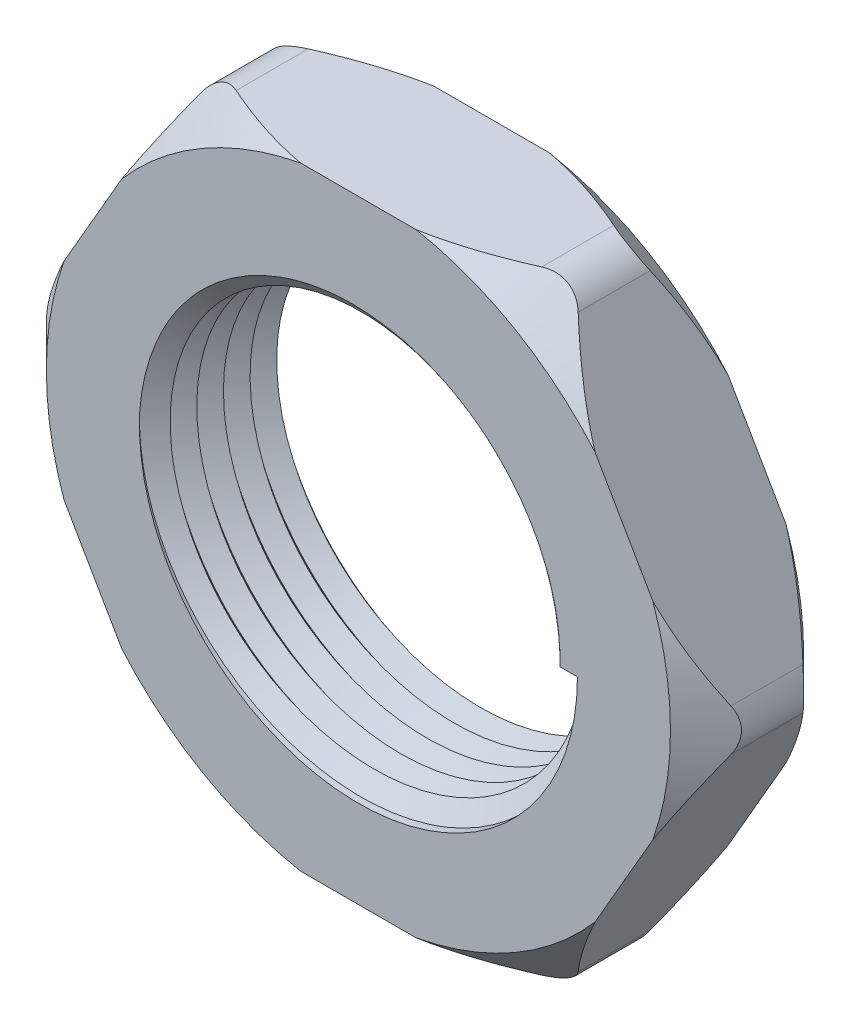
SolidWorks part; units mm, degrees
material "AISI 321 Annealed Stainless Steel (SS)"
ref_plane "Front Plane" through (0, 0, 0) normal (0, 0, 1) x (1, 0, 0)
ref_plane "Top Plane" through (0, 0, 0) normal (0, 1, 0) x (1, 0, 0)
ref_plane "Right Plane" through (0, 0, 0) normal (1, 0, 0) x (0, 0, -1)
sketch "Sketch1" plane through (0, 0, 0) normal (0, 0, 1) x (1, 0, 0)
  line L1 (12.8316, 0) -> (6.4158, 11.1125)
  line L2 (6.4158, 11.1125) -> (-6.4158, 11.1125)
  line L3 (-6.4158, 11.1125) -> (-12.8316, 0)
  line L4 (-12.8316, 0) -> (-6.4158, -11.1125)
  line L5 (-6.4158, -11.1125) -> (6.4158, -11.1125)
  line L6 (6.4158, -11.1125) -> (12.8316, 0)
  circle A0 centre (0, 0) radius 11.1125 construction
  circle A1 centre (0, 0) radius 7.9375
  dimension "D2" = 15.875
  dimension "D1" = 22.225
extrude "Boss-Extrude1" add sketch "Sketch1" along normal blind 4.826
sketch "Sketch2" plane through (0, 0, 0) normal (0, 1, 0) x (1, 0, 0)
  line L0 (11.3076, 0) -> (12.8316, -1.524)
  line L1 (12.8316, 0) -> (6.4158, 0) construction
  line L2 (12.8316, -4.826) -> (12.8316, 0) construction
  line L3 (12.8316, -1.524) -> (13.3729, -1.524)
  line L4 (13.3729, -1.524) -> (13.3729, 0.9545)
  line L5 (13.3729, 0.9545) -> (11.3076, 0.9545)
  line L6 (11.3076, 0.9545) -> (11.3076, 0)
  line L7 (12.8316, -3.302) -> (11.3076, -4.826)
  line L8 (12.8316, -4.826) -> (6.4158, -4.826) construction
  line L9 (11.3076, -4.826) -> (11.3076, -5.6615)
  line L10 (11.3076, -5.6615) -> (13.1981, -5.6615)
  line L11 (13.1981, -5.6615) -> (13.1981, -3.302)
  line L12 (13.1981, -3.302) -> (12.8316, -3.302)
  dimension "D1" = 1.524
  dimension "D2" = 1.524
  dimension "D3" = 1.524
  dimension "D4" = 1.524
sketch "Sketch4" plane through (0, 0, 0) normal (1, 0, 0) x (0, 0, -1)
  line L0 (0, 0) -> (-18.1067, 0) construction
  line L1 (-18.1067, 0) -> (9.9838, 0) construction
revolve "Cut-Revolve1" cut sketch "Sketch2" angle 360 about L0
fillet "Fillet2" radius 1.524 6 edges at (-12.8316, 0, 2.413) (-6.4158, -11.1125, 2.413) (6.4158, -11.1125, 2.413) (12.8316, 0, 2.413) (6.4158, 11.1125, 2.413) (-6.4158, 11.1125, 2.413)
sketch "Sketch5" plane through (0, 0, 0) normal (0, 0, 1) x (1, 0, 0)
  circle A0 centre (0, 0) radius 7.9375
  dimension "D1" = 15.875
curve "Helix/Spiral1" pitch 0.9652 height 4.826 radius 7.9375 left hand yes centre (0, 0, 0) axis (0, 0, 1) start towards (1, 0, 0)
ref_plane "Plane1" through (7.9375, 0, 4.826) normal (0, -0.9998, 0.0193) x (-1, 0, 0)
sketch "Sketch6" plane through (7.9375, 0, 4.826) normal (0, -0.9998, 0.0193) x (-1, 0, 0)
  line L0 (0, 0) -> (0, 5.6881) construction
  line L1 (-4.4542, 3.7326) -> (-4.4542, 1.122) construction
  line L2 (0, 1.4807) -> (0, -2.9127) construction
  line L3 (0, -2.9127) -> (0, 0) construction
  line L4 (0, 0) -> (1.27, 0) construction
  line L5 (0, -0.4762) -> (0.635, 0)
  line L6 (0.635, 0) -> (0, 0.4763)
  line L7 (0, 0.4763) -> (0, -0.4762)
  dimension "D1" = 0.635
  dimension "D2" = 0.9525
sweep "Sweep1" add profiles "Sketch6" path "Helix/Spiral1"
sketch "Sketch7" plane through (0, 0, 0) normal (0, 1, 0) x (1, 0, 0)
  line L0 (-8.578, 0) -> (-10.6695, 0) construction
  line L1 (-10.0468, 0) -> (11.8593, 0)
  line L2 (-10.0468, 0) -> (-10.0468, 1.3387)
  line L3 (-10.0468, 1.3387) -> (11.8593, 1.3387)
  line L4 (11.8593, 0) -> (11.8593, 1.3387)
  line L5 (10.6695, -4.826) -> (8.578, -4.826) construction
  line L6 (10.1133, -4.826) -> (-10.4237, -4.826)
  line L7 (10.1133, -4.826) -> (10.1133, -6.5746)
  line L8 (10.1133, -6.5746) -> (-10.4237, -6.5746)
  line L9 (-10.4237, -4.826) -> (-10.4237, -6.5746)
extrude "Cut-Extrude1" cut sketch "Sketch7" against normal mid plane 25.4
